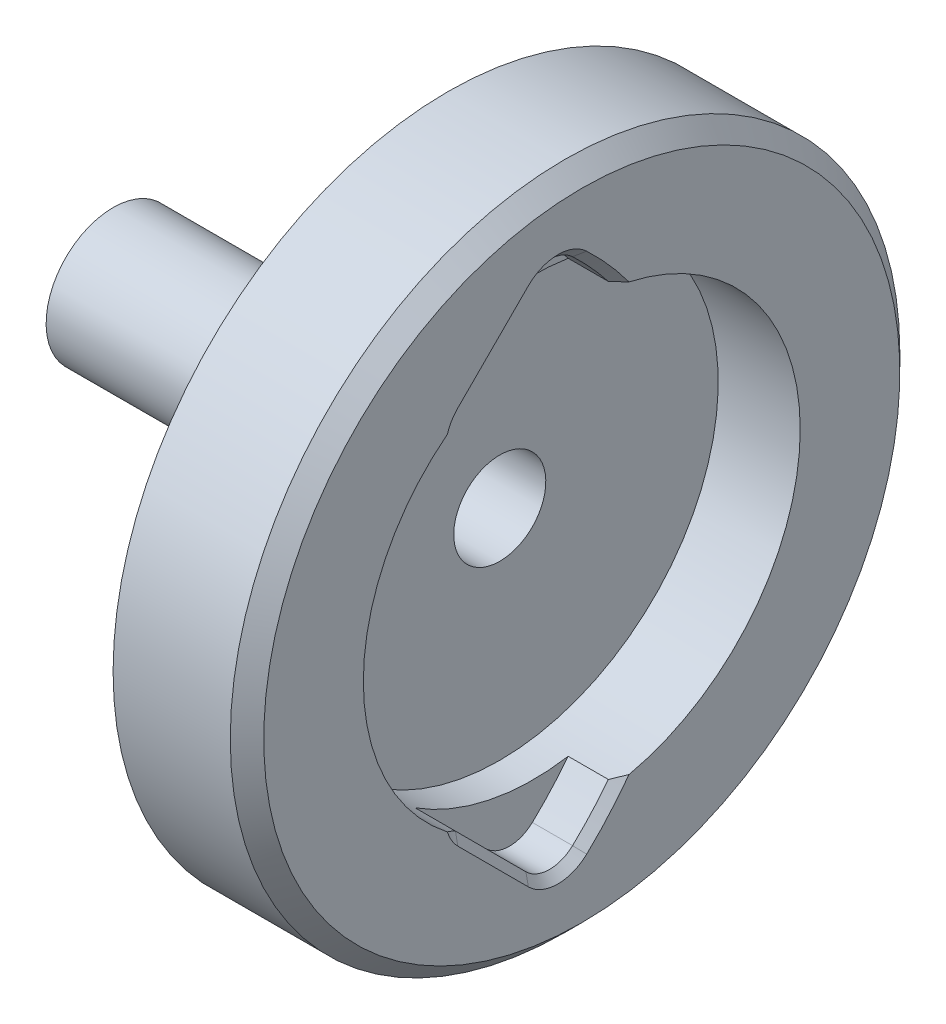
SolidWorks part; units mm, degrees
ref_plane "Alzado" through (0, 0, 0) normal (0, 0, 1) x (1, 0, 0)
ref_plane "Planta" through (0, 0, 0) normal (0, 1, 0) x (1, 0, 0)
ref_plane "Vista lateral" through (0, 0, 0) normal (1, 0, 0) x (0, 0, -1)
sketch "Croquis1" plane through (0, 0, 0) normal (0, 0, 1) x (1, 0, 0)
  line L0 (-20, 0) -> (-20, 4)
  line L1 (-20, 4) -> (0, 4)
  line L2 (0, 4) -> (0, 20)
  line L3 (0, 20) -> (8, 20)
  line L4 (8, 20) -> (8, 0)
  line L5 (8, 0) -> (-20, 0) construction
  line L6 (-20, 0) -> (8, 0)
  dimension "D1" = 40
  dimension "D2" = 8
  dimension "D3" = 20
  dimension "D4" = 8
revolve "Revolución1" add sketch "Croquis1" angle 360 about L5
sketch "Croquis2" plane through (8, 0, 0) normal (1, 0, 0) x (0, 0, -1)
  line L0 (0, 20) -> (0, -20) construction
  line L1 (-18.0333, 0) -> (-7.049, 10.9843) construction
  line L2 (-18.0333, 0) -> (-7.049, -10.9843) construction
  line L3 (-2.8392, 15.1941) -> (-7.049, 10.9843)
  line L4 (-7.049, -10.9843) -> (-2.8392, -15.1941)
  line L5 (-14.4333, 0) -> (-18.0333, 0) construction
  line L6 (-1.4538, 15.7797) -> (7.1943, 15.7797) construction
  line L7 (-1.4538, -15.7797) -> (8.9899, -15.7797) construction
  circle A0 centre (0, 0) radius 20 construction
  arc A1 (-0.0521, 15.2342) -> (-0.0521, -15.2342) centre (-14.4333, 0) cw
  arc A2 (-6.9884, 8.0978) -> (-6.9884, -8.0978) centre (-14.4333, 0) cw
  arc A3 (-0.0521, -15.2342) -> (-2.8392, -15.1941) centre (-1.425, -13.7799) cw
  arc A4 (-6.9884, -8.0978) -> (-7.049, -10.9843) centre (-5.6348, -9.5701) ccw
  arc A5 (-6.9884, 8.0978) -> (-7.049, 10.9843) centre (-5.6348, 9.5701) cw
  arc A6 (-0.0521, 15.2342) -> (-2.8392, 15.1941) centre (-1.425, 13.7799) ccw
  point P24 (-3.4333, 0)
  dimension "D1" = 20.95
  dimension "D2" = 11
  dimension "D4" = 2
  dimension "D3" = 90
  dimension "D5" = 3.6
extrude "Cortar-Extruir1" cut sketch "Croquis2" against normal blind 2.9
fillet "Redondeo1" radius 10 1 edges at (0, 4, 0)
sketch "Croquis3" plane through (-20, 0, 0) normal (-1, 0, 0) x (0, 0, 1)
  circle A0 centre (0, 0) radius 1.75
  dimension "D1" = 3.5
extrude "Cortar-Extruir2" cut sketch "Croquis3" against normal up to next
sketch "Croquis4" plane through (5.1, 0, 0) normal (1, 0, 0) x (0, 0, -1)
  circle A0 centre (0, 0) radius 2.75
  dimension "D1" = 5.5
extrude "Cortar-Extruir3" cut sketch "Croquis4" against normal offset from surface (22.1 mm away) 3 up to face at (-20, -1.75, 0)
chamfer "Chaflán1" distance 1 angle 45 1 edges at (8, 20, 0)
chamfer "Chaflán2" distance 0.5 angle 45 8 edges at (8, 0, 3.4333) (8, -9.5281, 7.6344) (8, 9.5281, 7.6344) (8, -13.0892, 4.9441) (8, 13.0892, 4.9441) (8, -15.7797, 1.4538) (8, 15.7797, 1.4538) (8, 0, -6.5167)
sketch "Croquis5" plane through (8, 0, 0) normal (1, 0, 0) x (0, 0, -1)
  circle A0 centre (0, 0) radius 13.05
  dimension "D1" = 26.1
extrude "Cortar-Extruir4" cut sketch "Croquis5" against normal offset from surface (4.9 mm away) 2 contours A0 up to face at (5.1, 2.75, 0) offset beyond the face yes
